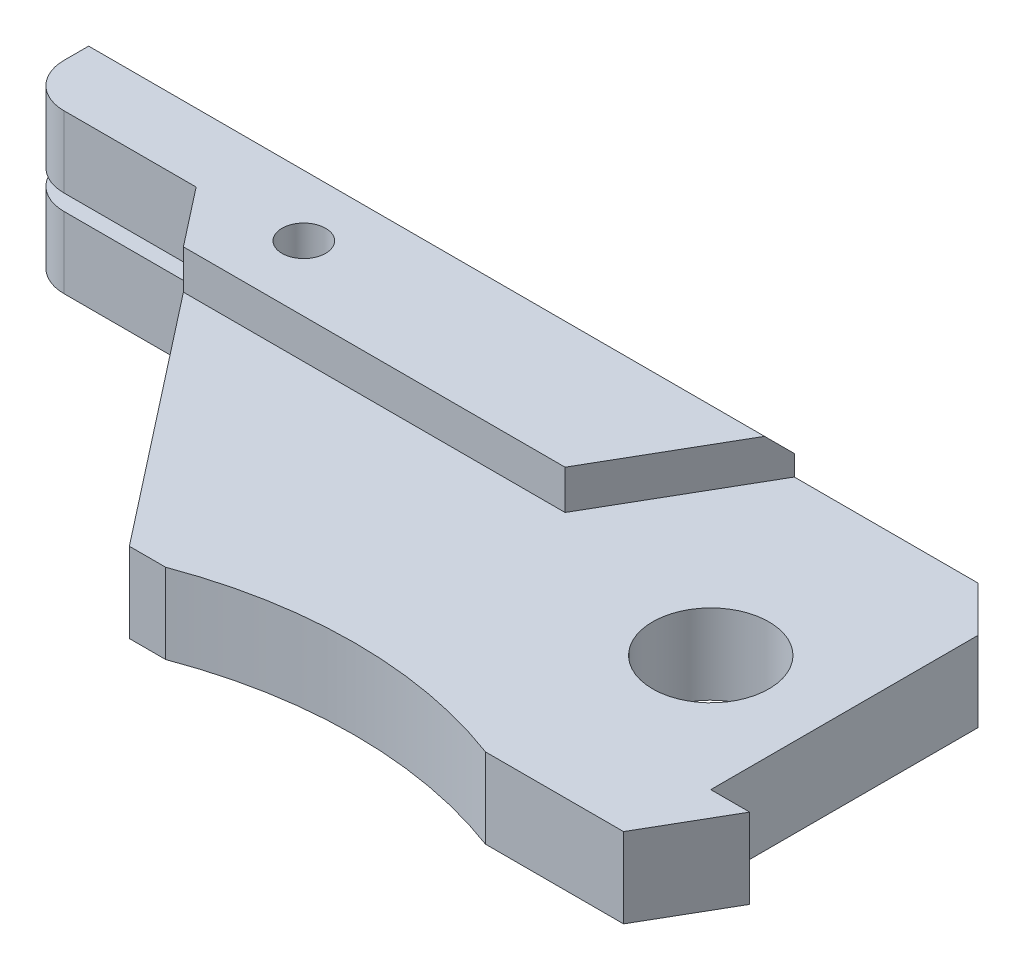
SolidWorks part; units mm, degrees
ref_plane "Front Plane" through (0, 0, 0) normal (0, 0, 1) x (1, 0, 0)
ref_plane "Top Plane" through (0, 0, 0) normal (0, 1, 0) x (1, 0, 0)
ref_plane "Right Plane" through (0, 0, 0) normal (1, 0, 0) x (0, 0, -1)
sketch "Sketch1" plane through (0, 0, 0) normal (0, 1, 0) x (1, 0, 0)
  line L0 (4.8848, 13.5) -> (-55, 13.5)
  line L1 (-42.907, 7.5) -> (-26.5, -13.5)
  line L2 (9.1924, 9.1924) -> (8, 10.3848) construction
  line L3 (8, 10.3848) -> (4.8848, 13.5)
  line L4 (7.5, -13.5) -> (-2, -13.5)
  line L5 (-24, -13.5) -> (-26.5, -13.5)
  line L6 (0, -13.5) -> (0, 13.5) construction
  line L7 (-13, -42.75) -> (-13, -11.5) construction
  line L8 (-29.6251, -9.5) -> (-7.3743, -9.5) construction
  line L9 (-7.3743, -9.5) -> (-23, 10.5) construction
  line L10 (-23, 10.5) -> (-55, 10.5) construction
  line L11 (-42.907, 7.5) -> (-55, 7.5)
  line L12 (-55, 7.5) -> (-55, 13.5)
  line L14 (8, 10.3848) -> (8, -8)
  line L15 (8, -8) -> (10.6754, -8)
  line L16 (10.6754, -8) -> (7.5, -13.5)
  circle A0 centre (0, 0) radius 4
  arc A1 (10.247, -8) -> (9.1924, 9.1924) centre (0, 0) ccw construction
  arc A2 (-2, -13.5) -> (-24, -13.5) centre (-13, -42.75) ccw
  circle A3 centre (-36, 8) radius 1.5
  dimension "D1" = 8
  dimension "D7" = 26.5
  dimension "D8" = 13
  dimension "D14" = 36
  dimension "D16" = 3
  dimension "D23" = 13
  dimension "D3" = 45
  dimension "D4" = 13.5
  dimension "D5" = 52
  dimension "D6" = 60
  dimension "D9" = 22
  dimension "D10" = 2
  dimension "D11" = 4
  dimension "D12" = 20
  dimension "D13" = 23
  dimension "D15" = 2.5
  dimension "D17" = 55
  dimension "D18" = 6
  dimension "D19" = 52
  dimension "D20" = 8
  dimension "D21" = 8
  dimension "D22" = 7.5
extrude "Boss-Extrude1" add sketch "Sketch1" along normal blind 2.75
sketch "Sketch2" plane through (0, 2.75, 0) normal (0, 1, 0) x (1, 0, 0)
  line L0 (-39.7819, 3.5) -> (-13.5235, 3.5)
  line L1 (-42.907, 7.5) -> (-26.5, -13.5) construction
  line L2 (-13.5235, 3.5) -> (-7.75, 13.5)
  line L3 (-55, 7.5) -> (-42.907, 7.5)
  line L4 (-7.75, 13.5) -> (-55, 13.5)
  line L5 (-42.907, 7.5) -> (-39.7819, 3.5)
  line L6 (4.8848, 13.5) -> (-55, 13.5) construction
  line L9 (-55, 13.5) -> (-55, 7.5)
  circle A0 centre (-36, 8) radius 1.5 construction
  circle A1 centre (-36, 8) radius 1.5
  dimension "D1" = 10
  dimension "D2" = 60
  dimension "D3" = 7.75
extrude "Boss-Extrude2" add sketch "Sketch2" along normal blind 2.7
sketch "Sketch3" plane through (0, 0, 0) normal (0, -1, 0) x (1, 0, 0)
  line L0 (-23, -10.5) -> (-55, -10.5) construction
  line L1 (-7.3743, 9.5) -> (-23, -10.5) construction
  line L2 (-29.6251, 9.5) -> (-7.3743, 9.5) construction
  line L3 (-23, -10.5) -> (-55, -10.5)
  line L4 (-7.3743, 9.5) -> (-23, -10.5)
  line L5 (-55, 9.5) -> (-7.3743, 9.5)
  line L7 (-55, -10.5) -> (-55, 9.5)
extrude "Cut-Extrude1" cut sketch "Sketch3" against normal blind 0.55
fillet "Fillet1" radius 3 1 edges at (-55, 3, -7.5)
chamfer "Chamfer1" distance 1.3 angle 45 1 edges at (-31.375, 5.45, -13.5)
mirror "Mirror1" about plane through (0, 0, 0) normal (0, 1, 0) of bodies 103
sketch "Sketch6" plane through (0, -5.45, 0) normal (0, -1, 0) x (1, 0, 0)
  line L0 (-32.2181, -3.5) -> (-28.3117, -8.5)
  line L1 (-39.7819, -3.5) -> (-13.5235, -3.5) construction
  line L2 (-28.3117, -8.5) -> (-10.6368, -8.5)
  line L3 (-13.5235, -3.5) -> (-8.5006, -12.2) construction
  line L4 (-10.6368, -8.5) -> (-13.5235, -3.5)
  line L5 (-13.5235, -3.5) -> (-32.2181, -3.5)
  line L6 (-39.7819, -3.5) -> (-32.2181, -3.5) construction
  line L7 (-36, -8) -> (-36, -3.5) construction
  circle A1 centre (-36, -8) radius 1.5 construction
  dimension "D1" = 8.5
  dimension "D2" = 52
extrude "Cut-Extrude3" cut sketch "Sketch6" against normal up to surface (2.7 mm away) up to face at (-8.2577, -2.75, 1.8287)
ref_axis "Axis1" through (0, 2.75, 0) along (0, -1, 0)
ref_plane "Plane1" through (0, 0, 0) normal (-0.0349, 0, 0.9994) x (0.9994, 0, 0.0349)
sketch "Sketch7" plane through (0, 0, 0) normal (-0.0349, 0, 0.9994) x (0.9994, 0, 0.0349)
  line L0 (-10, -10.9521) -> (-10, 49989.0479) construction
  line L1 (-10, -2.75) -> (-10, -1.75)
  line L2 (-12, -2.75) -> (-10, -2.75)
  line L3 (-10.9269, -2.75) -> (-28.5911, -2.75) construction
  arc A0 (-10, -1.75) -> (-12, -2.75) centre (-10, -4.25) ccw
  dimension "D2" = 4
  dimension "D1" = 1
  dimension "D3" = 10
revolve "Cut-Revolve1" cut sketch "Sketch7" angle 360 about L0
equation "\"Blade\"= 1.1"
equation "\"DoubleWall\"= 1.1"
equation "\"QuadWall\"= 2.2"
equation "\"Clearance\"= .5"
equation "\"D1@Boss-Extrude1\"  = \"Blade\" / 2 + \"QuadWall\""
equation "\"D1@Boss-Extrude2\" = \"Clearance\" + \"QuadWall\""
equation "\"D1@Cut-Extrude1\"=\"Blade\"/2"
